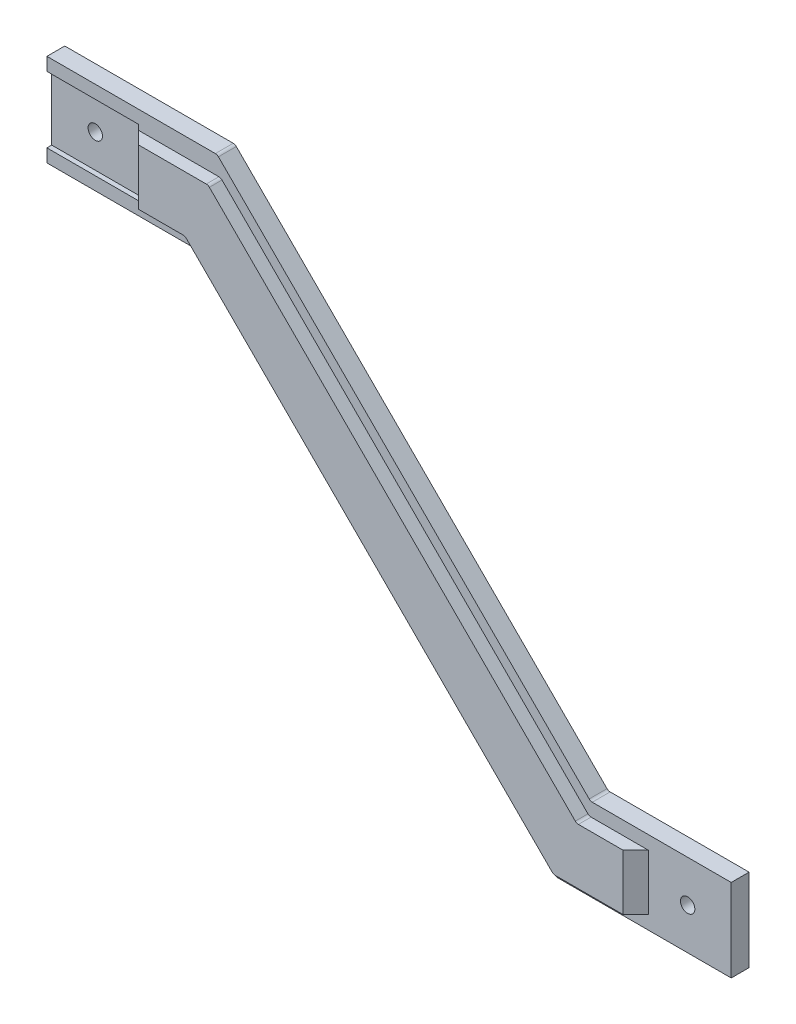
SolidWorks part; units mm, degrees
ref_plane "前视基准面" through (0, 0, 0) normal (0, 0, 1) x (1, 0, 0)
ref_plane "上视基准面" through (0, 0, 0) normal (0, 1, 0) x (1, 0, 0)
ref_plane "右视基准面" through (0, 0, 0) normal (1, 0, 0) x (0, 0, -1)
sketch "草图1" plane through (0, 0, 0) normal (0, 0, 1) x (1, 0, 0)
  line L0 (-78.55, 51.8) -> (-38.365, 51.8)
  line L1 (-38.365, 51.8) -> (46.235, -32.8)
  line L2 (46.235, -32.8) -> (78.55, -32.8)
  line L3 (78.55, -32.8) -> (78.55, -51.8)
  line L4 (78.55, -51.8) -> (38.365, -51.8)
  line L5 (38.365, -51.8) -> (-46.235, 32.8)
  line L6 (-46.235, 32.8) -> (-78.55, 32.8)
  line L7 (-78.55, 32.8) -> (-78.55, 51.8)
  line L8 (-38.365, 51.8) -> (38.365, -51.8) construction
  line L9 (-46.235, 32.8) -> (46.235, -32.8) construction
  circle A0 centre (-68.55, 42.3) radius 1.65
  circle A1 centre (68.55, -42.3) radius 1.65
  dimension "D2" = 3.3
  dimension "D1" = 19
  dimension "D3" = 137.1
  dimension "D4" = 84.6
  dimension "D5" = 9.5
  dimension "D6" = 9.5
  dimension "D7" = 135
  dimension "D8" = 19
  dimension "D9" = 10
  dimension "D10" = 10
extrude "凸台-拉伸1" add sketch "草图1" along normal blind 3
sketch "草图2" plane through (0, 0, 3) normal (0, 0, 1) x (1, 0, 0)
  line L0 (-57.55, 48.7) -> (-57.55, 35.9)
  line L1 (-57.55, 35.9) -> (-43.951, 35.9)
  line L2 (-43.951, 35.9) -> (40.649, -48.7)
  line L3 (40.649, -48.7) -> (59.55, -48.7)
  line L4 (59.55, -48.7) -> (59.55, -35.9)
  line L5 (59.55, -35.9) -> (45.951, -35.9)
  line L6 (45.951, -35.9) -> (-38.649, 48.7)
  line L7 (-38.649, 48.7) -> (-57.55, 48.7)
  line L8 (-38.365, 51.8) -> (-78.55, 51.8) construction
  line L9 (38.365, -51.8) -> (78.55, -51.8) construction
  line L10 (78.55, -51.8) -> (78.55, -32.8) construction
  line L11 (-78.55, 51.8) -> (-78.55, 32.8) construction
  line L12 (46.235, -32.8) -> (-38.365, 51.8) construction
  dimension "D1" = 12.8
  dimension "D2" = 12.8
  dimension "D3" = 3.1
  dimension "D4" = 3.1
  dimension "D5" = 19
  dimension "D6" = 21
  dimension "D7" = 12.8
extrude "凸台-拉伸2" add sketch "草图2" along normal blind 2.9
chamfer "倒角1" distance 2.9 angle 45 2 edges at (59.55, -42.3, 5.9) (-57.55, 42.3, 5.9)
sketch "草图6" plane through (0, 0, 0) normal (0, 0, 1) x (1, 0, 0)
  line L0 (-78.55, 52.9) -> (-78.55, 31.7)
  line L1 (-78.55, 31.7) -> (-45.135, 31.7)
  line L2 (-46.235, 32.8) -> (38.365, -51.8) construction
  line L3 (-45.135, 31.7) -> (38.365, -51.8)
  line L4 (38.365, -51.8) -> (78.55, -51.8)
  line L5 (78.55, -51.8) -> (78.55, -32.8)
  line L6 (78.55, -32.8) -> (46.235, -32.8)
  line L7 (46.235, -32.8) -> (-39.465, 52.9)
  line L8 (-39.465, 52.9) -> (-78.55, 52.9)
  line L9 (-78.55, 51.8) -> (-78.55, 32.8) construction
  line L10 (-78.55, 32.8) -> (-46.235, 32.8) construction
  circle A0 centre (-68.55, 42.3) radius 1.65
  circle A1 centre (68.55, -42.3) radius 1.65
  dimension "D3" = 3.3
  dimension "D1" = 21.2
  dimension "D2" = 1.1
extrude "凸台-拉伸3" add sketch "草图6" against normal blind 4.1 from offset 3
sketch "草图7" plane through (0, 0, 0) normal (0, 0, 1) x (1, 0, 0)
  line L0 (-78.55, 49.9) -> (-78.55, 34.7)
  line L1 (-78.55, 34.7) -> (-57.55, 34.7)
  line L3 (-57.55, 34.7) -> (-57.55, 49.9)
  line L5 (-57.55, 49.9) -> (-78.55, 49.9)
  line L6 (-39.465, 52.9) -> (-78.55, 52.9) construction
  line L7 (-78.55, 31.7) -> (-45.135, 31.7) construction
  line L8 (-78.55, 52.9) -> (-78.55, 31.7) construction
  dimension "D1" = 21
  dimension "D2" = 3
  dimension "D3" = 3
extrude "切除-拉伸1" cut sketch "草图7" against normal blind 1.1 from offset 3
fillet "圆角1" radius 1 8 edges at (-38.649, 48.7, 4.45) (-39.465, 52.9, 0.95) (46.235, -32.8, 0.95) (45.951, -35.9, 4.45) (38.365, -51.8, 0.95) (40.649, -48.7, 4.45) (-43.951, 35.9, 4.45) (-45.135, 31.7, 0.95)
